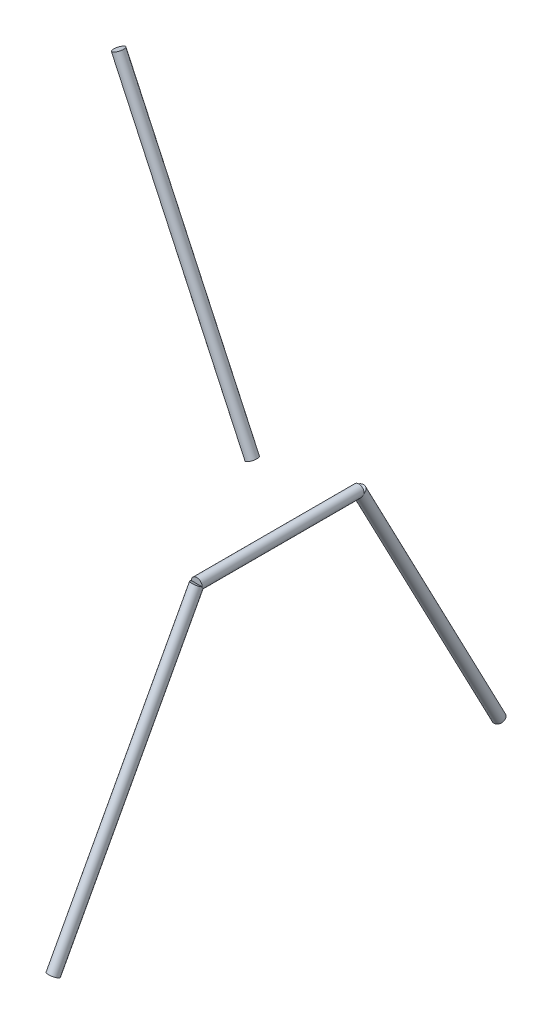
SolidWorks part; units mm, degrees
ref_plane "Alzado" through (0, 0, 0) normal (0, 0, 1) x (1, 0, 0)
ref_plane "Planta" through (0, 0, 0) normal (0, 1, 0) x (1, 0, 0)
ref_plane "Vista lateral" through (0, 0, 0) normal (1, 0, 0) x (0, 0, -1)
sketch3d "Sk_Cable_puente_1"
  line L0 (424.6109, 411.5791, -33) -> (424.8763, 451.3903, -12)
  dimension "D1" = 45.0111
sweep "Cable_puente_1" add path "Sk_Cable_puente_1" circular profile diameter 1.6 parameters "D3"=1.6
sketch3d "Sk_Cable_puente_2"
  line L0 (424.8763, 451.3903, -12) -> (424.8763, 451.3903, 12)
sweep "Cable_puente_2" add path "Sk_Cable_puente_2" circular profile diameter 1.6 parameters "D3"=1.6
sketch3d "Sk_Cable_puente_3"
  line L0 (424.8763, 451.3903, 12) -> (424.6109, 411.5791, 33)
  dimension "D1" = 45.0111
sweep "Cable_puente_3" add path "Sk_Cable_puente_3" circular profile diameter 1.6 parameters "D3"=1.6
sketch3d "Sk_Cable_tiro"
  line L0 (421.0876, 459.554, 0) -> (401.3021, 502.1865, 0)
  dimension "D1" = 47
sweep "Cable_tiro" add path "Sk_Cable_tiro" circular profile diameter 1.6 parameters "D3"=1.6
